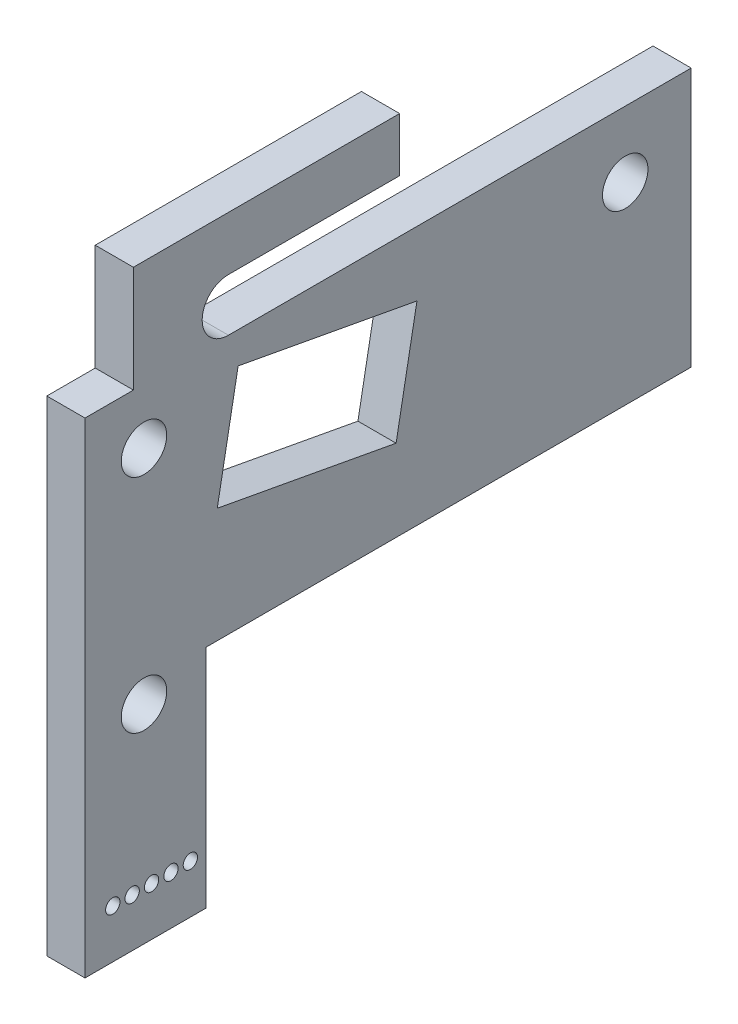
SolidWorks part; units mm, degrees
ref_plane "Front Plane" through (0, 0, 0) normal (0, 0, 1) x (1, 0, 0)
ref_plane "Top Plane" through (0, 0, 0) normal (0, 1, 0) x (1, 0, 0)
ref_plane "Right Plane" through (0, 0, 0) normal (1, 0, 0) x (0, 0, -1)
sketch "Sketch1" plane through (0, 0, 0) normal (1, 0, 0) x (0, 0, -1)
  line L0 (-56.5904, 6.9096) -> (-51.5186, 6.9096)
  line L1 (-56.5904, 6.9096) -> (-56.5904, -43.8904)
  line L2 (-56.5904, -43.8904) -> (-43.8904, -43.8904)
  line L3 (-43.8904, -43.8904) -> (-43.8904, -20.2221)
  line L4 (-43.8904, -20.2221) -> (6.9096, -20.2221)
  line L5 (6.9096, -20.2221) -> (6.9096, 6.9096)
  line L6 (0, 6.9096) -> (0, 0) construction
  line L7 (6.9096, 0) -> (0, 0) construction
  line L8 (-40.5479, 3.6124) -> (-21.8156, 0.1475)
  line L9 (-40.5479, 3.6124) -> (-42.7334, -8.2033)
  line L10 (-21.8156, 0.1475) -> (-24.0012, -11.6682)
  line L11 (-42.7334, -8.2033) -> (-24.0012, -11.6682)
  line L12 (-45.553, -38.8104) -> (-47.585, -38.8104) construction
  line L13 (-41.5653, 12.4119) -> (-23.6308, 12.4119)
  line L14 (-23.6308, 12.4119) -> (-23.6308, 18.0537)
  line L15 (-23.6308, 18.0537) -> (-51.5186, 18.0537)
  line L16 (-51.5186, 18.0537) -> (-51.5186, 6.9096)
  line L17 (-41.5653, 6.9096) -> (6.9096, 6.9096)
  line L18 (-42.0241, 11.3574) -> (-36.9578, 23.003) construction
  circle A0 centre (0, 0) radius 2.3813
  circle A1 centre (-45.553, -38.8104) radius 0.75
  circle A2 centre (-47.585, -38.8104) radius 0.75
  circle A3 centre (-49.617, -38.8104) radius 0.75
  circle A4 centre (-51.649, -38.8104) radius 0.75
  circle A5 centre (-50.4101, -22.1372) radius 2.3812
  circle A6 centre (-50.4101, 1.0794) radius 2.3812
  circle A7 centre (-53.681, -38.8104) radius 0.75
  arc A8 (-41.5653, 6.9096) -> (-41.5653, 12.4119) centre (-41.5653, 9.6608) cw
  dimension "D1" = 4.7625
  dimension "D2" = 1.5
  dimension "D3" = 5.08
  dimension "D5" = 2.032
  dimension "D6" = 19.05
  dimension "D4" = 5
extrude "Boss-Extrude1" add sketch "Sketch1" along normal mid plane 4
